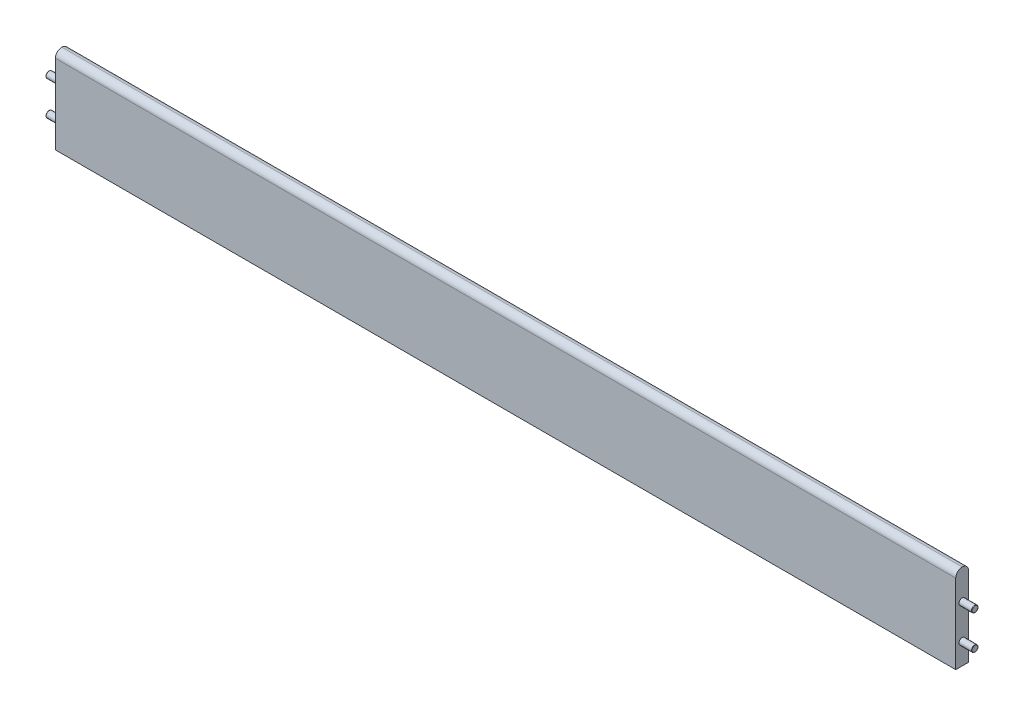
SolidWorks part; units mm, degrees
material "Faggio"
ref_plane "Piano frontale" through (0, 0, 0) normal (0, 0, 1) x (1, 0, 0)
ref_plane "Piano superiore" through (0, 0, 0) normal (0, 1, 0) x (1, 0, 0)
ref_plane "Piano destro" through (0, 0, 0) normal (1, 0, 0) x (0, 0, -1)
sketch "Schizzo1" plane through (0, 0, 0) normal (0, 0, 1) x (1, 0, 0)
  line L1 (0, 0) -> (2100, 0)
  line L2 (0, 0) -> (0, -200)
  line L3 (0, -200) -> (2100, -200)
  line L4 (2100, 0) -> (2100, -200)
  dimension "D1" = 2100
  dimension "D2" = 200
extrude "Estrusione-Estrusione1" add sketch "Schizzo1" along normal blind 30
fillet "Raccordo1" radius 15 2 edges at (1050, 0, 0) (1050, 0, 30)
sketch "Schizzo3" plane through (2100, 0, 0) normal (1, 0, 0) x (0, 0, -1)
  line L0 (0, -200) -> (0, -15) construction
  line L1 (-30, -200) -> (0, -200) construction
  circle A0 centre (-15, -70) radius 7.5
  circle A1 centre (-15, -150) radius 7.5
  dimension "D1" = 15
  dimension "D3" = 15
  dimension "D4" = 15
  dimension "D2" = 15
  dimension "D5" = 80
  dimension "D6" = 50
extrude "Estrusione-Estrusione2" add sketch "Schizzo3" along normal blind 30
fillet "Raccordo2" radius 1 2 edges at (2130, -150, 7.5) (2130, -70, 7.5)
sketch "Schizzo4" plane through (0, 0, 0) normal (-1, 0, 0) x (0, 0, 1)
  line L0 (30, -15) -> (30, -200) construction
  line L1 (30, -200) -> (0, -200) construction
  circle A0 centre (15, -70) radius 7.5
  circle A1 centre (15, -150) radius 7.5
  dimension "D1" = 15
  dimension "D2" = 15
  dimension "D3" = 80
  dimension "D4" = 15
  dimension "D5" = 15
  dimension "D6" = 50
extrude "Estrusione-Estrusione3" add sketch "Schizzo4" along normal blind 30
fillet "Raccordo3" radius 1 2 edges at (-30, -157.5, 15) (-30, -77.5, 15)
